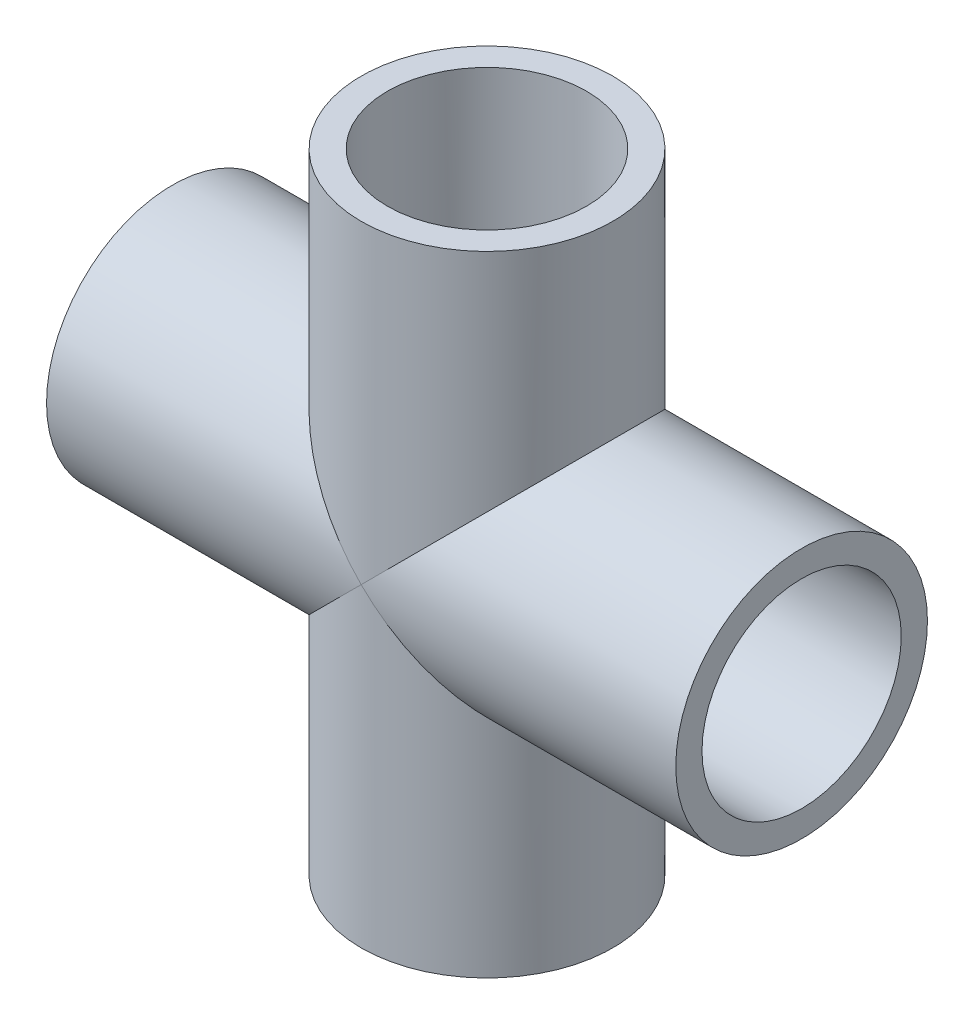
SolidWorks part; units mm, degrees
material "PVC Rigid"
ref_plane "Front Plane" through (0, 0, 0) normal (0, 0, 1) x (1, 0, 0)
ref_plane "Top Plane" through (0, 0, 0) normal (0, 1, 0) x (1, 0, 0)
ref_plane "Right Plane" through (0, 0, 0) normal (1, 0, 0) x (0, 0, -1)
sketch "Sketch1" plane through (0, 0, 0) normal (1, 0, 0) x (0, 0, -1)
  circle A0 centre (0, 0) radius 24.13
  circle A1 centre (0, 0) radius 30.48
  dimension "D1" = 6.35
  dimension "D2" = 48.26
extrude "Boss-Extrude1" add sketch "Sketch1" along normal blind 152.4
sketch "Sketch2" plane through (0, 0, 0) normal (0, 1, 0) x (1, 0, 0)
  line L0 (0, 30.48) -> (0, -30.48) construction
  circle A0 centre (76.2, 0) radius 30.48
  circle A1 centre (76.2, 0) radius 24.13
  dimension "D1" = 6.35
  dimension "D2" = 48.26
  dimension "D3" = 76.2
extrude "Boss-Extrude2" add sketch "Sketch2" along normal blind 76.2 and the other way blind 76.2
sketch "Sketch4" plane through (0, 0, 0) normal (0, 0, 1) x (1, 0, 0)
  circle A0 centre (76.2, 0) radius 3.175
  dimension "D1" = 6.35
extrude "Cut-Extrude1" cut sketch "Sketch4" against normal through all
ref_axis "Axis1" through (76.2, 0, -30.48) along (0, 0, 1)
